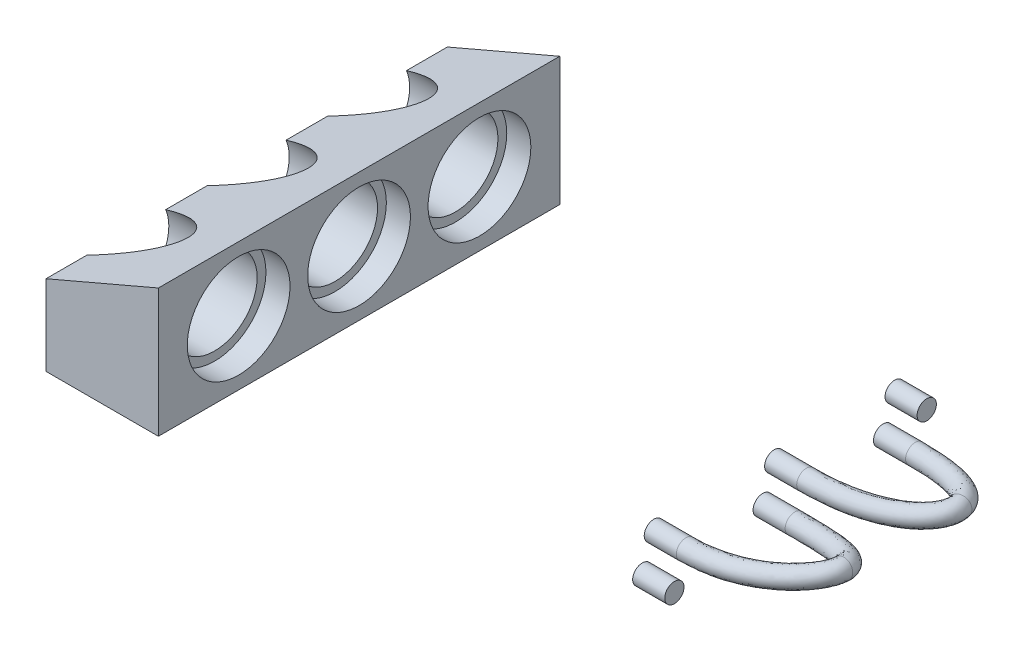
SolidWorks part; units mm, degrees
material "ABS"
ref_plane "Plan de face" through (0, 0, 0) normal (0, 0, 1) x (1, 0, 0)
ref_plane "Plan de dessus" through (0, 0, 0) normal (0, 1, 0) x (1, 0, 0)
ref_plane "Plan de droite" through (0, 0, 0) normal (1, 0, 0) x (0, 0, -1)
sketch "Esquisse1" plane through (0, 0, 0) normal (0, 0, 1) x (1, 0, 0)
  line L0 (0, 0) -> (7, 0)
  line L1 (7, 0) -> (7, 8)
  line L2 (7, 8) -> (0, 5)
  line L3 (0, 5) -> (0, 0)
  dimension "D1" = 5
  dimension "D2" = 8
  dimension "D3" = 7
extrude "Boss.-Extru.1" add sketch "Esquisse1" along normal blind 25
sketch "Esquisse2" plane through (0, 0, 0) normal (-1, 0, 0) x (0, 0, 1)
  line L0 (0, 0) -> (0, 4) construction
  line L1 (0, 5) -> (0, 0) construction
  line L2 (0, 4) -> (5, 4) construction
  line L3 (5, 4) -> (12.5, 4) construction
  line L4 (12.5, 4) -> (20, 4) construction
  line L5 (20, 4) -> (25, 4) construction
  line L6 (25, 5) -> (25, 0) construction
  circle A0 centre (5, 4) radius 2.65
  circle A1 centre (12.5, 4) radius 2.65
  circle A2 centre (20, 4) radius 2.65
  dimension "D2" = 5.3
  dimension "D1" = 4
  dimension "D3" = 5
extrude "Enlèv. mat.-Extru.1" cut sketch "Esquisse2" against normal through all
sketch "Esquisse3" plane through (7, 0, 0) normal (1, 0, 0) x (0, 0, -1)
  circle A0 centre (-20, 4) radius 3.2
  circle A1 centre (-12.5, 4) radius 3.2
  circle A2 centre (-5, 4) radius 3.2
  dimension "D1" = 6.4
extrude "Enlèv. mat.-Extru.2" cut sketch "Esquisse3" against normal blind 1.5
sketch "Esquisse5" plane through (31.5, 0, 0) normal (1, 0, 0) x (0, 0, -1)
  line L0 (-18.88, 4.24) -> (-18.4, 3.76) construction
  line L1 (-18.88, 3.76) -> (-18.4, 3.76) construction
  line L2 (-11.38, 4.24) -> (-10.9, 3.76) construction
  line L3 (-3.88, 4.24) -> (-3.4, 3.76) construction
  circle A0 centre (-18.64, 4) radius 0.6
  circle A1 centre (-11.14, 4) radius 0.6
  circle A2 centre (-3.64, 4) radius 0.6
  dimension "D1" = 1.2
extrude "Boss.-Extru.2" add sketch "Esquisse5" along normal blind 2 separate body
sketch "Esquisse6" plane through (33.5, 0, 0) normal (1, 0, 0) x (0, 0, -1)
  line L0 (-6.6, 4.24) -> (-6.12, 3.76) construction
  line L1 (-14.1, 4.24) -> (-13.62, 3.76) construction
  line L2 (-21.6, 4.24) -> (-21.12, 3.76) construction
  circle A0 centre (-21.36, 4) radius 0.6
  circle A1 centre (-13.86, 4) radius 0.6
  circle A2 centre (-6.36, 4) radius 0.6
  dimension "D1" = 1.2
extrude "Boss.-Extru.3" add sketch "Esquisse6" along normal blind 2 separate body
sketch3d "Esquisse3D1"
  line L0 (33.5, 4, 18.64) -> (31.5, 4, 18.64) construction
  line L1 (33.5, 4, 18.64) -> (31.5, 4, 18.64) construction
  line L2 (35.5, 4, 13.86) -> (33.5, 4, 13.86) construction
  line L3 (35.5, 4, 13.86) -> (33.5, 4, 13.86) construction
  spline S0 degree 3 poles (33.5, 4, 18.64) (37.4359, 4, 18.64) (41.9319, 5.2663, 15.5745) (38.7083, 4, 13.86) (35.5, 4, 13.86) knots 0 0 0 0 0.600954 1 1 1 1
  point P9 (36.6071, -1.6903, 14.2406)
  point P10 (40.925, 3.5729, 14.0909)
  point P11 (40.7882, 3.7696, 15.8599)
sweep "Balayage1" add path "Esquisse3D1" circular profile diameter 1.2 parameters "D3"=1.2
sketch3d "Esquisse3D2"
  line L0 (33.5, 4, 11.14) -> (31.5, 4, 11.14) construction
  line L1 (33.5, 4, 11.14) -> (31.5, 4, 11.14) construction
  line L2 (33.5, 4, 6.36) -> (35.5, 4, 6.36) construction
  line L3 (35.5, 4, 6.36) -> (33.5, 4, 6.36) construction
  spline S0 degree 3 poles (33.5, 4, 11.14) (38.2492, 4, 11.14) (42.0021, 4.7726, 8.4694) (38.3848, 4, 6.36) (35.5, 4, 6.36) knots 0 0 0 0 0.593818 1 1 1 1
  point P9 (46.7291, 5.2732, 7.1331)
  point P10 (44.8693, 7.2086, 6.9195)
  point P11 (42.9059, 4.1054, 4.84)
  point P12 (42.8032, 5.556, 7.863)
  point P13 (41.043, 3.9012, 6.5514)
  point P14 (40.0731, 4.5953, 8.7907)
  point P15 (40.1074, 4.3727, 8.1662)
sweep "Balayage2" add path "Esquisse3D2" circular profile diameter 1.2 parameters "D3"=1.2
